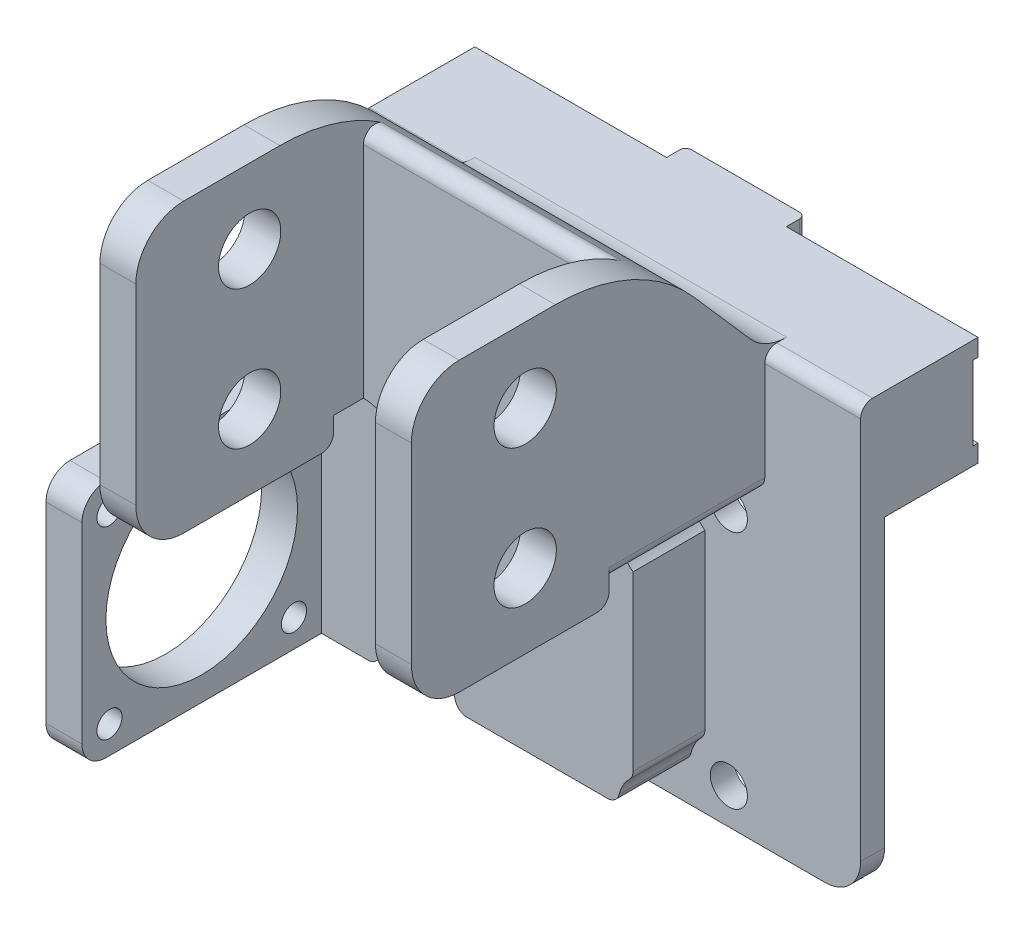
SolidWorks part; units mm, degrees
material "6063-T5"
ref_plane "Front Plane" through (0, 0, 0) normal (1, 0, 0) x (0, 1, 0)
ref_plane "Top Plane" through (0, 0, 0) normal (0, 0, 1) x (0, 1, 0)
ref_plane "Right Plane" through (0, 0, 0) normal (0, 1, 0) x (-1, 0, 0)
sketch "Sketch1" plane through (0, 0, 0) normal (0, 0, 1) x (0, 1, 0)
  line L0 (-13, 0) -> (0, 0) construction
  line L5 (-13, 21) -> (23, 21)
  line L6 (-13, 21) -> (-13, -21)
  line L7 (-10, -10) -> (10, -10) construction
  line L8 (-10, -10) -> (-10, 10) construction
  line L9 (-10, 10) -> (10, 10) construction
  line L10 (10, -10) -> (10, 10) construction
  line L11 (-10, -10) -> (10, 10) construction
  line L12 (-10, 10) -> (10, -10) construction
  line L13 (-13, -21) -> (23, -21)
  line L14 (23, 21) -> (23, -21)
  circle A0 centre (-10, -10) radius 1.55
  circle A1 centre (10, -10) radius 1.55
  circle A2 centre (10, 10) radius 1.55
  circle A3 centre (-10, 10) radius 1.55
  point P0 (0, 0)
  point P5 (0, 0)
  dimension "D2" = 3.1
  dimension "D1" = 20
  dimension "D3" = 42
  dimension "D4" = 13
  dimension "D5" = 23
extrude "Boss-Extrude1" add sketch "Sketch1" along normal blind 2
sketch "Sketch5" plane through (0, 0, 0) normal (0, 0, 1) x (1, 0, 0)
  line L0 (21, -13) -> (21, 23) construction
  line L1 (-21, 23) -> (21, 23)
  line L2 (-21, 23) -> (-21, 13.9)
  line L3 (-21, 13.9) -> (21, 13.9)
  line L4 (21, 23) -> (21, 13.9)
  dimension "D1" = 9.1
extrude "Boss-Extrude2" add sketch "Sketch5" against normal blind 7.4
sketch "Sketch6" plane through (0, 0, -7.4) normal (0, 0, -1) x (1, 0, 0)
  line L0 (-21, -13.9) -> (21, -13.9) construction
  line L3 (-5, -13.9) -> (5, -13.9)
  line L4 (-5, -13.9) -> (-5, -23)
  line L5 (-5, -23) -> (5, -23)
  line L6 (5, -13.9) -> (5, -23)
  line L7 (21, -23) -> (-21, -23) construction
  line L8 (0, -13.9) -> (0, 0) construction
  dimension "D1" = 10
extrude "Boss-Extrude3" add sketch "Sketch6" along normal blind 2
sketch "Sketch2" plane through (0, 0, -9.4) normal (0, 0, -1) x (1, 0, 0)
  line L0 (-21, -18.5) -> (21, -18.5) construction
  line L1 (-21, -13.9) -> (-21, 13) construction
  line L2 (21, 13) -> (21, -13.9) construction
  line L3 (21, -23) -> (-21, -23) construction
  line L5 (-20, -23) -> (20, -23)
  line L6 (-20, -23) -> (-20, -14)
  line L7 (-20, -14) -> (20, -14)
  line L8 (20, -23) -> (20, -14)
  line L9 (-20, -23) -> (20, -14) construction
  line L10 (-20, -14) -> (20, -23) construction
  circle A0 centre (0, -18.5) radius 3
  dimension "D1" = 4.5
  dimension "D2" = 6
  dimension "D3" = 9
  dimension "D4" = 40
extrude "Cut-Extrude1" cut sketch "Sketch2" against normal blind 6 contours A0 region at (0, 18.5, -9.4)
sketch "Sketch4" plane through (0, 0, -7.4) normal (0, 0, -1) x (1, 0, 0)
  line L0 (-5, -13.9) -> (-5, -23) construction
  line L15 (-21, -13.9) -> (-5, -13.9)
  line L16 (-21, -13.9) -> (-21, -15.35)
  line L17 (-21, -15.35) -> (-5, -15.35)
  line L18 (-5, -13.9) -> (-5, -15.35)
  line L19 (-21, -23) -> (-21, -13.9) construction
  line L20 (-5, -23) -> (-21, -23)
  line L21 (-5, -23) -> (-5, -21.55)
  line L22 (-5, -21.55) -> (-21, -21.55)
  line L23 (-21, -23) -> (-21, -21.55)
  line L24 (5, -23) -> (5, -13.9) construction
  line L25 (21, -13.9) -> (5, -13.9)
  line L26 (21, -13.9) -> (21, -15.35)
  line L27 (21, -15.35) -> (5, -15.35)
  line L28 (5, -13.9) -> (5, -15.35)
  line L29 (21, -13.9) -> (21, -23) construction
  line L30 (5, -23) -> (21, -23)
  line L31 (5, -23) -> (5, -21.55)
  line L32 (5, -21.55) -> (21, -21.55)
  line L33 (21, -23) -> (21, -21.55)
  dimension "D1" = 6.2
extrude "Boss-Extrude4" add sketch "Sketch4" along normal blind 0.4
fillet "Fillet2" radius 3 2 edges at (-21, -13, 1) (21, -13, 1)
fillet "Fillet3" radius 0.5 2 edges at (5, 18.45, -9.4) (-5, 18.45, -9.4)
sketch "Sketch7" plane through (0, 0, 2) normal (0, 0, 1) x (1, 0, 0)
  line L10 (0, 0) -> (8, 0) construction
  line L11 (-21, -10) -> (8, -10)
  line L12 (-21, -10) -> (-21, 10)
  line L13 (-21, 10) -> (8, 10)
  line L14 (8, -10) -> (8, 10)
  line L15 (-21, 23) -> (-21, -10) construction
  dimension "D1" = 20
  dimension "D2" = 29
extrude "Boss-Extrude5" add sketch "Sketch7" along normal blind 6
sketch "Sketch8" plane through (-21, 0, 0) normal (-1, 0, 0) x (0, -1, 0)
  line L0 (-10, 18) -> (10, 18) construction
  line L1 (-10, 8) -> (10, 8)
  line L2 (-10, 8) -> (-10, 28)
  line L3 (-10, 28) -> (10, 28)
  line L4 (10, 8) -> (10, 28)
  line L6 (-7.7, 10.3) -> (7.7, 10.3) construction
  line L7 (-7.7, 10.3) -> (-7.7, 25.7) construction
  line L8 (-7.7, 25.7) -> (7.7, 25.7) construction
  line L9 (7.7, 10.3) -> (7.7, 25.7) construction
  line L10 (-7.7, 10.3) -> (7.7, 25.7) construction
  line L11 (-7.7, 25.7) -> (7.7, 10.3) construction
  circle A0 centre (0, 18) radius 8
  circle A2 centre (7.7, 25.7) radius 1.05
  circle A3 centre (7.7, 10.3) radius 1.05
  circle A4 centre (-7.7, 25.7) radius 1.05
  circle A5 centre (-7.7, 10.3) radius 1.05
  dimension "D1" = 15.4
  dimension "D2" = 2.1
  dimension "D3" = 16
extrude "Boss-Extrude6" add sketch "Sketch8" against normal blind 3
fillet "Fillet4" radius 2 2 edges at (-19.5, -10, 28) (-19.5, 10, 28)
ref_plane "Plane1" through (-10, 0, 0) normal (-1, 0, 0) x (0, 1, 0)
sketch "Sketch10" plane through (-10, 0, 0) normal (-1, 0, 0) x (0, 1, 0)
  line L0 (0, 0) -> (0, -22) construction
  line L1 (35, -31.5) -> (11, -31.5)
  line L2 (35, -31.5) -> (35, -12.5)
  line L3 (35, -12.5) -> (11, -12.5)
  line L4 (11, -31.5) -> (11, -12.5)
  line L5 (0, -22) -> (11, -22) construction
  line L6 (11, -22) -> (17.2222, -22) construction
  line L7 (17.2222, -22) -> (28.7778, -22) construction
  line L8 (28.7778, -22) -> (35, -22) construction
  circle A0 centre (28.7778, -22) radius 2.6
  circle A1 centre (17.2222, -22) radius 2.6
  circle A2 centre (28.7778, -22) radius 4.75 construction
  circle A3 centre (17.2222, -22) radius 4.75 construction
  point P13 (17.443, -20)
  point P16 (27.1353, -20)
  point P17 (26.9289, -20)
  point P18 (16.2146, -20)
  point P19 (17.2222, -20)
  dimension "D4" = 5.2
  dimension "D5" = 9.5
  dimension "D1" = 19
  dimension "D2" = 24
  dimension "D3" = 22
  dimension "D6" = 11
extrude "Boss-Extrude7" add sketch "Sketch10" along normal blind 3 separate body
mirror "Mirror1" about plane through (0, 0, 0) normal (1, 0, 0) of bodies 120
sketch "Sketch14" plane through (0, 0, 12.5) normal (0, 0, -1) x (1, 0, 0)
  line L0 (13, -35) -> (13, -11) construction
  line L1 (-13, -35) -> (13, -35)
  line L2 (-13, -35) -> (-13, -10)
  line L3 (-13, -10) -> (13, -10)
  line L4 (13, -35) -> (13, -10)
  line L5 (8, -10) -> (-18, -10) construction
  point P4 (0, 0)
  point P5 (0, 0)
  point P8 (11.7061, -4.354)
  dimension "D1" = 26
extrude "Boss-Extrude8" add sketch "Sketch14" along normal up to surface (10.5 mm away) up to face at (-3.4615, 0.6736, 2)
sketch "Sketch15" plane through (13, 0, 0) normal (1, 0, 0) x (0, 1, 0)
  line L0 (23, 2) -> (29.7492, 7.9056)
  line L1 (35, 2) -> (35, 31.5) construction
  line L2 (35, 12.5) -> (35, 2)
  line L3 (35, 2) -> (23, 2)
  line L5 (35, 12.5) -> (11, 12.5) construction
  line L6 (35, 19.4771) -> (35, 12.5)
  line L7 (12.3701, 12.5) -> (10, 8)
  line L8 (10, 8) -> (10, 12.5)
  line L9 (10, 12.5) -> (12.3701, 12.5)
  arc A0 (35, 19.4771) -> (29.7492, 7.9056) centre (19.6241, 19.4771) cw
  point P18 (0, 0)
  point P19 (0, 0)
  point P20 (0, 0)
  point P21 (31.068, 7.7148)
  point P22 (0, 0)
  point P23 (13.0304, 12.5)
  point P24 (12.3701, 12.5)
  dimension "D1" = 15.9452
extrude "Cut-Extrude3" cut sketch "Sketch15" against normal up to surface (26 mm away) up to face at (-13, 18.125, 12.75)
sketch "Sketch9" plane through (0, 0, 2) normal (0, 0, 1) x (1, 0, 0)
  circle A0 centre (-10, 10) radius 3.25
  circle A1 centre (10, 10) radius 3.25
  circle A2 centre (10, -10) radius 3.25
  circle A3 centre (-10, -10) radius 3.25
  dimension "D1" = 6.5
extrude "Cut-Extrude2" cut sketch "Sketch9" along normal blind 13
fillet "Fillet6" radius 1 10 edges at (-13, 11.25, 13.75) (-13, 11.25, 6.1867) (-13.25, 10, 5) (-6.75, -10, 5) (-13.25, -10, 5) (8, -7.4383, 5) (6.75, -10, 5) (13, 11.25, 6.1867) (13, 11.25, 13.75) (0, 12.3701, 12.5)
fillet "Fillet7" radius 1 2 edges at (11.5, 11, 15) (-11.5, 11, 15)
fillet "Fillet8" radius 4 5 edges at (0, 23, 2) (11.5, 11, 31.5) (11.5, 35, 31.5) (-11.5, 35, 31.5) (-11.5, 11, 31.5)
fillet "Fillet9" radius 1 2 edges at (-17, 23, 2) (17, 23, 2)
fillet "Fillet10" radius 1 1 edges at (0, 33.3259, 12.5)
ref_axis "Axis1" through (13, 28.7778, 22) along (-1, 0, 0)
